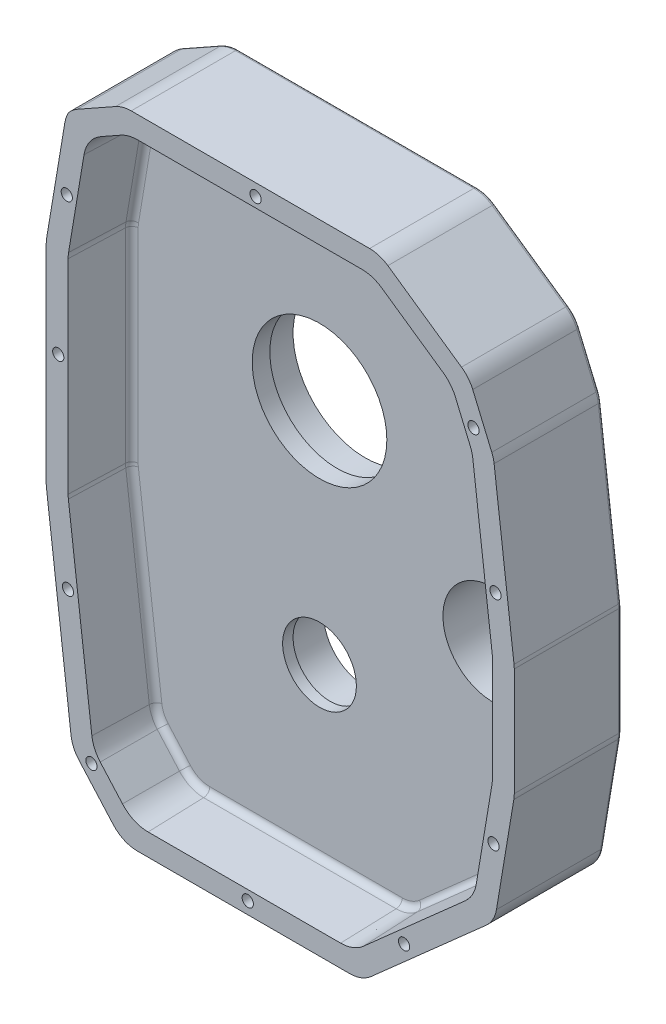
SolidWorks part; units mm, degrees
note: The reader was unsure of these and kept them because the rebuilt part matched: shared geometry of "Schizzo1<2>".
ref_plane "Piano frontale" through (0, 0, 0) normal (0, 0, 1) x (1, 0, 0)
ref_plane "Piano superiore" through (0, 0, 0) normal (0, 1, 0) x (1, 0, 0)
ref_plane "Piano destro" through (0, 0, 0) normal (1, 0, 0) x (0, 0, -1)
sketch "Schizzo1" plane through (0, 0, 0) normal (0, 0, 1) x (1, 0, 0)
  line L0 (59.972, -9.5487) -> (184.1074, -9.5487)
  line L4 (195.1963, 388.4513) -> (251.0014, 349.7307)
  line L5 (251.0014, 349.7307) -> (266.2641, 313.838)
  line L6 (266.9069, 63.8243) -> (184.1074, -9.5487)
  line L12 (266.2641, 313.838) -> (279.1827, 207.629)
  line L13 (279.1827, 207.629) -> (279.1827, 137.3778)
  line L14 (279.1827, 137.3778) -> (266.9069, 63.8243)
  line L15 (195.1963, 388.4513) -> (34.9751, 388.4513)
  line L18 (-12.8173, 291.7963) -> (-12.8173, 270.1406)
  line L19 (-12.8173, 270.1406) -> (-12.8173, 159.5427)
  line L22 (-12.8173, 159.5427) -> (-8.0968, 120.7332)
  line L23 (-8.0968, 120.7332) -> (-1.2777, 64.671)
  line L24 (-1.2777, 64.671) -> (3.4183, 26.0624)
  line L25 (3.4183, 26.0624) -> (34.9751, -9.5487)
  line L26 (34.9751, -9.5487) -> (59.972, -9.5487)
  line L27 (-12.8173, 291.7963) -> (-0.4488, 365.9057)
  line L28 (-0.4488, 365.9057) -> (2.5692, 370.2553)
  line L29 (2.5692, 370.2553) -> (34.9751, 388.4513)
  dimension "D1" = 398
  dimension "D2" = 292
extrude "Estrusione-Estrusione1" add sketch "Schizzo1" along normal blind 77
sketch "Schizzo2" plane through (0, 0, 77) normal (0, 0, 1) x (1, 0, 0)
  line L0 (119.1827, 251.9513) -> (119.1827, 109.4513) construction
  line L1 (227.1858, 174.3461) -> (119.1827, 109.4513) construction
  line L2 (119.1827, 109.4513) -> (200.5095, 109.4513) construction
  line L3 (34.9751, -9.5487) -> (184.1074, -9.5487) construction
  line L6 (-12.8173, 291.7963) -> (-12.8173, 159.5427) construction
  circle A0 centre (119.1827, 251.9513) radius 45
  circle A1 centre (227.1858, 174.3461) radius 31
  circle A2 centre (119.1827, 109.4513) radius 26
  dimension "D1" = 62
  dimension "D2" = 52
  dimension "D3" = 90
  dimension "D7" = 119
  dimension "D8" = 132
  dimension "D4" = 142.5
  dimension "D5" = 126
  dimension "D6" = 31
extrude "Taglio-Estrusione1" cut sketch "Schizzo2" against normal through all
sketch "Schizzo4" plane through (0, 0, 0) normal (0, 0, -1) x (-1, 0, 0)
  line L482 (-190.5021, 373.4513) -> (-238.8923, 339.8755)
  line L483 (-238.8923, 339.8755) -> (-251.63, 309.9207)
  line L484 (-251.63, 309.9207) -> (-264.1827, 206.7201)
  line L485 (-264.1827, 206.7201) -> (-264.1827, 138.6209)
  line L486 (-264.1827, 138.6209) -> (-252.9855, 71.5298)
  line L487 (-252.9855, 71.5298) -> (-178.4176, 5.4513)
  line L488 (-178.4176, 5.4513) -> (-41.7249, 5.4513)
  line L489 (-41.7249, 5.4513) -> (-17.7443, 32.5128)
  line L490 (-17.7443, 32.5128) -> (-2.1827, 160.4516)
  line L491 (-2.1827, 160.4516) -> (-2.1827, 290.5532)
  line L492 (-2.1827, 290.5532) -> (-13.6521, 359.2755)
  line L494 (-13.6521, 359.2755) -> (-38.8983, 373.4513)
  line L495 (-38.8983, 373.4513) -> (-190.5021, 373.4513)
  line L496 (-190.5021, 373.4513) -> (-238.8923, 339.8755)
  line L497 (-238.8923, 339.8755) -> (-251.63, 309.9207)
  line L498 (-251.63, 309.9207) -> (-264.1827, 206.7201)
  line L499 (-264.1827, 206.7201) -> (-264.1827, 138.6209)
  line L500 (-264.1827, 138.6209) -> (-252.9855, 71.5298)
  line L501 (-252.9855, 71.5298) -> (-178.4176, 5.4513)
  line L502 (-178.4176, 5.4513) -> (-41.7249, 5.4513)
  line L503 (-41.7249, 5.4513) -> (-17.7443, 32.5128)
  line L504 (-17.7443, 32.5128) -> (-2.1827, 160.4516)
  line L505 (-2.1827, 160.4516) -> (-2.1827, 290.5532)
  line L506 (-2.1827, 290.5532) -> (-13.6521, 359.2755)
  line L508 (-13.6521, 359.2755) -> (-38.8983, 373.4513)
  line L509 (-38.8983, 373.4513) -> (-190.5021, 373.4513)
  dimension "D1" = 15
extrude "Taglio-Estrusione2" cut sketch "Schizzo4" against normal blind 48.5
sketch "Schizzo8" plane through (0, 0, 77) normal (0, 0, 1) x (1, 0, 0)
  circle A3 centre (227.1858, 174.3461) radius 39
  circle A4 centre (119.1827, 251.9513) radius 60
  circle A5 centre (119.1827, 109.4513) radius 34
  point P2 (227.1858, 213.3461)
  point P5 (119.1827, 311.9513)
  point P6 (260.9607, 154.8461)
  point P7 (193.4108, 154.8461)
  point P8 (227.1858, 174.3461)
  point P13 (119.1827, 143.4513)
  point P14 (171.1442, 221.9513)
  point P15 (67.2212, 221.9513)
  point P16 (119.1827, 251.9513)
  point P21 (148.6275, 92.4513)
  point P22 (89.7378, 92.4513)
  point P23 (119.1827, 109.4513)
  dimension "D1" = 78
  dimension "D2" = 3
  dimension "100" = 120
  dimension "82" = 68
  dimension "D7" = 0
  dimension "D8" = 0
  dimension "D9" = 0
  dimension "D4" = 3
  dimension "D6" = 3
hole_wizard "Foro filettato M8-1" positions "Schizzo3D2" profile "Schizzo9" tap size "M8" standard "ISO"
sketch3d "Schizzo3D2"
  point P0 (119.1827, 311.9513, 77)
  point P3 (67.2212, 221.9513, 77)
  point P6 (171.1442, 221.9513, 77)
  point P9 (227.1858, 213.3461, 77)
  point P12 (193.4108, 154.8461, 77)
  point P15 (260.9607, 154.8461, 77)
  point P18 (119.1827, 143.4513, 77)
  point P21 (89.7378, 92.4513, 77)
  point P24 (148.6275, 92.4513, 77)
sketch "Schizzo9" plane through (119.1827, 311.9513, 77) normal (1, 0, 0) x (0, -1, 0)
  line L0 (0, 0) -> (0, 25.0429)
  line L1 (0, 25.0429) -> (3.4, 23)
  line L2 (3.4, 23) -> (3.4, 0.625)
  line L3 (3.4, 0.625) -> (4.025, 0)
  line L5 (4.025, 0) -> (0, 0)
  line L6 (-3.4, 0.625) -> (-4.025, 0) construction
  line L10 (0, 25.0429) -> (-3.4, 23) construction
  line L11 (0, -6.35) -> (0, 107.95) construction
  dimension "Tap Drill Dia." = 6.8
  dimension "Tap Drill Depth" = 23
  dimension "Near C'Sink Dia." = 8.05
  dimension "Near C'Sink Angle" = 90
  dimension "Drill Angle" = 118
cosmetic thread "Filettatura del foro19" parameters "D1"=20, "D2"=7.8
cosmetic thread "Filettatura del foro20" parameters "D1"=20, "D2"=7.8
cosmetic thread "Filettatura del foro21" parameters "D1"=20, "D2"=7.8
cosmetic thread "Filettatura del foro22" parameters "D1"=20, "D2"=7.8
cosmetic thread "Filettatura del foro23" parameters "D1"=20, "D2"=7.8
cosmetic thread "Filettatura del foro24" parameters "D1"=20, "D2"=7.8
cosmetic thread "Filettatura del foro25" parameters "D1"=20, "D2"=7.8
cosmetic thread "Filettatura del foro26" parameters "D1"=20, "D2"=7.8
cosmetic thread "Filettatura del foro27" parameters "D1"=20, "D2"=7.8
sketch "Schizzo10" plane through (0, 0, 0) normal (0, 0, -1) x (-1, 0, 0)
  line L0 (-279.1827, 207.629) -> (-266.2641, 313.838) construction
  line L1 (-238.8923, 339.8755) -> (-251.63, 309.9207) construction
  line L3 (-117.8071, 388.4513) -> (-117.8071, 377.4513) construction
  line L4 (-195.1963, 388.4513) -> (-34.9751, 388.4513) construction
  line L5 (-7.3292, 321.3901) -> (7.3349, 324.6457) construction
  line L6 (0.4488, 365.9057) -> (12.8173, 291.7963) construction
  line L7 (-246.6828, 321.5548) -> (-260.949, 326.3373) construction
  line L8 (-238.8923, 339.8755) -> (-251.63, 309.9207) construction
  line L9 (-266.2641, 313.838) -> (-251.0014, 349.7307) construction
  line L10 (-260.0187, 240.9543) -> (-274.9437, 242.4794) construction
  line L11 (-251.63, 309.9207) -> (-264.1827, 206.7201) construction
  line L12 (-2.1827, 234.1317) -> (12.8173, 234.1317) construction
  line L13 (-2.1827, 160.4516) -> (-2.1827, 290.5532) construction
  line L14 (12.8173, 291.7963) -> (12.8173, 159.5427) construction
  line L15 (-8.2207, 110.8103) -> (6.6695, 108.9992) construction
  line L16 (-17.7443, 32.5128) -> (-2.1827, 160.4516) construction
  line L17 (12.8173, 159.5427) -> (-3.4183, 26.0624) construction
  line L18 (-112.9191, 5.4513) -> (-112.9191, -9.5487) construction
  line L19 (-34.9751, -9.5487) -> (-184.1074, -9.5487) construction
  line L20 (-203.9893, 28.1118) -> (-216.4303, 19.0943) construction
  line L21 (-252.9855, 71.5298) -> (-178.4176, 5.4513) construction
  line L22 (-258.8828, 106.865) -> (-273.6267, 104.0879) construction
  line L23 (-210.4191, 23.4513) -> (-15.4191, 23.4513) construction
  line L24 (-264.1827, 138.6209) -> (-252.9855, 71.5298) construction
  line L25 (-184.1074, -9.5487) -> (-266.9069, 63.8243) construction
  line L26 (-2.1827, 290.5532) -> (-13.6521, 359.2755) construction
  line L27 (-38.8983, 373.4513) -> (-190.5021, 373.4513) construction
  line L28 (-41.7249, 5.4513) -> (-17.7443, 32.5128) construction
  line L30 (-178.4176, 5.4513) -> (-41.7249, 5.4513) construction
  line L31 (-251.63, 309.9207) -> (-264.1827, 206.7201) construction
  circle A0 centre (-117.8071, 380.9513) radius 3.5
  circle A1 centre (-253.772, 324.0494) radius 3.5
  circle A4 centre (5.3173, 234.1317) radius 3.5
  circle A5 centre (-266.2547, 105.4764) radius 3.5
  circle A6 centre (-0.7392, 110.2036) radius 3.5
  circle A10 centre (-112.9191, -2.0487) radius 3.5
  circle A11 centre (0.0028, 323.0179) radius 3.5
  circle A12 centre (-267.4812, 241.7168) radius 3.5
  circle A13 centre (-210.4191, 23.4513) radius 3.5
  circle A14 centre (-15.4191, 23.4513) radius 3.5
  point P15 (-266.2547, 105.4764)
  dimension "D1" = 7
  dimension "10" = 7
  dimension "D3" = 7
  dimension "D4" = 7
  dimension "D5" = 7
  dimension "D6" = 7
  dimension "6" = 7
  dimension "D7" = 25.5
  dimension "D8" = 7
  dimension "D9" = 7.5
  dimension "7" = 7
  dimension "D16" = 7.5
  dimension "D17" = 7
  dimension "D10" = 7.5
  dimension "D11" = 7.5
  dimension "D12" = 7.5
  dimension "D13" = 7.5
  dimension "D14" = 7.5
  dimension "D15" = 7.5
  dimension "D18" = 97.5
  dimension "D19" = 97.5
  dimension "D20" = 25.5
  dimension "D21" = 7.75
extrude "Taglio-Estrusione3" cut sketch "Schizzo10" against normal through all
mirror "Specchia1" of "Taglio-Estrusione1", "Estrusione-Estrusione1", "Taglio-Estrusione2", "Foro filettato M8-1", "Taglio-Estrusione3"
cosmetic thread "Filettatura del foro28" parameters "D1"=20, "D2"=7.8
cosmetic thread "Filettatura del foro29" parameters "D1"=20, "D2"=7.8
cosmetic thread "Filettatura del foro30" parameters "D1"=20, "D2"=7.8
cosmetic thread "Filettatura del foro31" parameters "D1"=20, "D2"=7.8
cosmetic thread "Filettatura del foro32" parameters "D1"=20, "D2"=7.8
cosmetic thread "Filettatura del foro33" parameters "D1"=20, "D2"=7.8
cosmetic thread "Filettatura del foro34" parameters "D1"=20, "D2"=7.8
cosmetic thread "Filettatura del foro35" parameters "D1"=20, "D2"=7.8
cosmetic thread "Filettatura del foro36" parameters "D1"=20, "D2"=7.8
extrude "Taglio-Estrusione4" cut sketch "Schizzo1<2>" against normal blind 87 from offset 77
sketch "Schizzo1<2>" plane through (0, 0, 0) normal (0, 0, 1) x (1, 0, 0) same geometry as "Schizzo1"
fillet "Raccordo1" radius 20 14 edges at (195.1963, 388.4513, -43.5) (34.9751, 388.4513, -43.5) (-0.4488, 365.9057, -43.5) (2.5692, 370.2553, -43.5) (-12.8173, 291.7963, -43.5) (-12.8173, 159.5427, -43.5) (3.4183, 26.0624, -43.5) (34.9751, -9.5487, -43.5) (184.1074, -9.5487, -43.5) (266.9069, 63.8243, -43.5) (279.1827, 137.3778, -43.5) (279.1827, 207.629, -43.5) (266.2641, 313.838, -43.5) (251.0014, 349.7307, -43.5)
fillet "Raccordo2" radius 2 27 edges at (-0.3253, 364.8301, -77) (3.6392, 370.4906, -77) (18.4991, 379.2, -77) (35.1453, 387.8005, -77) (114.5717, 388.4513, -77) (194.9106, 387.5385, -77) (223.298, 368.9528, -77) (250.3678, 349.215, -77) (259.209, 330.4291, -77) (266.0718, 313.7865, -77) (272.821, 259.9309, -77) (279.1461, 207.6268, -77) (279.1827, 172.7262, -77) (279.1143, 137.3834, -77) (273.491, 103.2744, -77) (265.8434, 64.4129, -77) (225.6973, 27.3063, -77) (183.6142, -8.2485, -77) (110.2479, -9.5487, -77) (35.7677, -7.7872, -77) (18.2787, 9.2928, -77) (4.283, 26.4517, -77) (-5.0025, 95.2939, -77) (-12.7807, 159.5449, -77) (-12.8173, 225.4467, -77) (-12.749, 291.7906, -77) (-6.8658, 327.4564, -77)
sketch "Schizzo11" plane through (0, 0, -48.5) normal (0, 0, 1) x (1, 0, 0)
  circle A0 centre (227.1858, 174.3461) radius 26
  circle A1 centre (227.1858, 174.3461) radius 23
  dimension "D1" = 46
  dimension "D2" = 52
extrude "Estrusione-Estrusione2" [suppressed] add sketch "Schizzo11" against normal blind 8
sketch "Schizzo12" plane through (0, 0, -48.5) normal (0, 0, 1) x (1, 0, 0)
  circle A0 centre (119.1827, 251.9513) radius 45
  circle A1 centre (119.1827, 251.9513) radius 42
  dimension "D1" = 84
  dimension "D2" = 90
extrude "Estrusione-Estrusione3" add sketch "Schizzo12" against normal blind 11
sketch "Schizzo13" plane through (0, 0, -48.5) normal (0, 0, 1) x (1, 0, 0)
  circle A0 centre (119.1827, 109.4513) radius 26
  circle A1 centre (119.1827, 109.4513) radius 23
  dimension "D1" = 46
  dimension "D2" = 52
extrude "Estrusione-Estrusione4" add sketch "Schizzo13" against normal blind 6.5
sketch "Schizzo14" [suppressed] plane through (0, 0, -10) normal (0, 0, 1) x (1, 0, 0)
  line L0 (279.1827, 139.0353) -> (279.1827, 206.4171) construction
  line L1 (271.6827, 159.3461) -> (-59.1341, 159.3461) construction
  line L2 (-12.671, 158.3397) -> (2.6659, 32.2481) construction
  circle A0 centre (271.6827, 159.3461) radius 3
  circle A1 centre (227.1858, 174.3461) radius 23 construction
  circle A2 centre (-3.6569, 146.3461) radius 3
  dimension "D1" = 6
  dimension "D2" = 7.5
  dimension "D3" = 13
  dimension "D4" = 7.5
  dimension "6" = 6
  dimension "15" = 15
extrude "Taglio-Estrusione5" [suppressed] cut sketch "Schizzo14" against normal blind 11
fillet "Raccordo3" [suppressed] radius 4
fillet "Raccordo4" radius 20 13 edges at (264.1827, 138.6209, -29.25) (252.9855, 71.5298, -29.25) (178.4176, 5.4513, -29.25) (264.1827, 206.7201, -29.25) (251.63, 309.9207, -29.25) (238.8923, 339.8755, -29.25) (41.7249, 5.4513, -29.25) (17.7443, 32.5128, -29.25) (2.1827, 160.4516, -29.25) (190.5021, 373.4513, -29.25) (2.1827, 290.5532, -29.25) (13.6521, 359.2755, -29.25) (38.8983, 373.4513, -29.25)
draft "Sformo1" type of draft neutral plane draft angle 2 faces to draft 1 face at (114.1862, 373.4513, -29.25) neutral plane through (0, 0, -48.5) neutral plane normal (0, 0, 1) parameters "D1"=2
fillet "Raccordo5" radius 4 26 edges at (39.0685, 372.8005, -48.5) (28.1733, 367.4292, -48.5) (15.4345, 358.0237, -48.5) (7.2649, 321.0048, -48.5) (2.251, 290.5475, -48.5) (2.1827, 225.2796, -48.5) (2.2193, 160.4539, -48.5) (9.6605, 98.9736, -48.5) (18.609, 32.9022, -48.5) (28.8166, 20.018, -48.5) (42.5175, 7.2128, -48.5) (110.7779, 5.4513, -48.5) (177.9244, 6.7515, -48.5) (215.8917, 38.6591, -48.5) (251.9219, 72.1185, -48.5) (259.0303, 107.7488, -48.5) (264.1143, 138.6266, -48.5) (264.1827, 172.8933, -48.5) (264.1461, 206.7179, -48.5) (258.004, 257.5178, -48.5) (251.4377, 309.8692, -48.5) (245.8374, 323.5429, -48.5) (238.2587, 339.3599, -48.5) (214.8963, 356.5252, -48.5) (190.2164, 372.5385, -48.5) (114.1862, 373.4513, -48.5)
